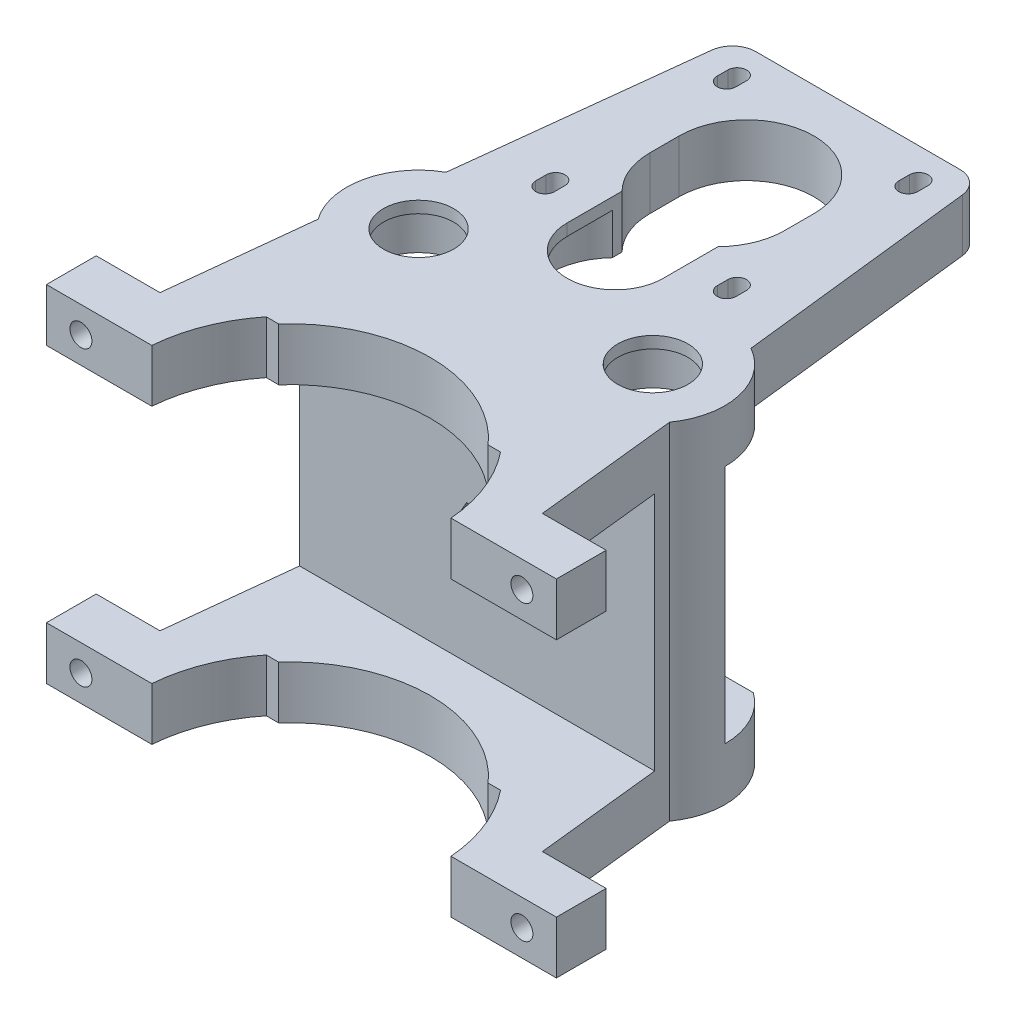
SolidWorks part; units mm, degrees
ref_plane "Alzado" through (0, 0, 0) normal (0, 0, 1) x (1, 0, 0)
ref_plane "Planta" through (0, 0, 0) normal (0, 1, 0) x (1, 0, 0)
ref_plane "Vista lateral" through (0, 0, 0) normal (1, 0, 0) x (0, 0, -1)
sketch "Croquis1" plane through (0, 0, 0) normal (0, 1, 0) x (1, 0, 0)
  line L0 (0, 78) -> (0, 73) construction
  line L1 (0, 78) -> (0, 55.57) construction
  line L2 (0, 73) -> (0, 78) construction
  line L3 (-11.5, 73) -> (-11.5, 78)
  line L4 (11.5, 73) -> (11.5, 78)
  line L5 (0, 78) -> (0, 55.57) construction
  line L6 (8.2, 78) -> (8.2, 55.57)
  line L7 (-8.2, 78) -> (-8.2, 55.57)
  line L8 (0, 0) -> (0, 10.5) construction
  line L9 (-25.5343, 2) -> (-43.5343, 2)
  line L10 (-43.5343, 2) -> (-43.5343, 10.5)
  line L11 (-43.5343, 10.5) -> (-32.6458, 10.5)
  line L12 (17.8885, 16) -> (20, 16)
  line L13 (-20, 16) -> (-17.8885, 16)
  line L14 (-32.6458, 10.5) -> (-30.0085, 34.8564)
  line L16 (26.0326, 52.719) -> (21, 97)
  line L17 (21, 97) -> (-21, 97)
  line L18 (-21, 97) -> (-26.0265, 52.7183)
  line L27 (25.5343, 2) -> (43.5343, 2)
  line L28 (43.5343, 2) -> (43.5343, 10.5)
  line L29 (43.5343, 10.5) -> (32.6458, 10.5)
  line L30 (32.6458, 10.5) -> (30.0091, 34.851)
  line L68 (-15.5, 91) -> (15.5, 91) construction
  line L69 (-15.5, 91) -> (-15.5, 60) construction
  line L70 (-15.5, 60) -> (15.5, 60) construction
  line L71 (15.5, 91) -> (15.5, 60) construction
  line L72 (-15.5, 91) -> (15.5, 60) construction
  line L73 (-15.5, 60) -> (15.5, 91) construction
  arc A0 (-11.5, 73) -> (11.5, 73) centre (0, 73) ccw
  arc A1 (11.5, 78) -> (-11.5, 78) centre (0, 78) ccw
  arc A2 (8.2, 78) -> (-8.2, 78) centre (0, 78) ccw
  arc A3 (-8.2, 55.57) -> (8.2, 55.57) centre (0, 55.57) ccw
  arc A4 (-25.5343, 2) -> (-20, 16) centre (0, 0) cw
  circle A12 centre (20, 42) radius 6
  circle A13 centre (-20, 42) radius 6
  arc A15 (17.8885, 16) -> (-17.8885, 16) centre (0, 0) ccw
  arc A18 (25.5343, 2) -> (20, 16) centre (0, 0) ccw
  arc A21 (-26.0265, 52.7183) -> (-30.0085, 34.8564) centre (-20, 42) ccw
  arc A28 (30.0091, 34.851) -> (26.0326, 52.719) centre (20, 42) ccw
  point P4 (0, 75.5)
  point P7 (0, 66.785)
  point P10 (0, 75.5)
  point P23 (0, 66.785)
  point P36 (0, 97)
  point P56 (0, 72.1)
  point P151 (0, 72.1)
  dimension "D4" = 24
  dimension "D10" = 12.2964
  dimension "D11" = 12.3
  dimension "D12" = 12
  dimension "D19" = 5
  dimension "D20" = 22.43
  dimension "D21" = 19
  dimension "D24" = 8.2
  dimension "D26" = 6
  dimension "D28" = 42
  dimension "D22" = 55
  dimension "D23" = 11.5
  dimension "D5" = 25.6125
  dimension "D3" = 40
  dimension "D6" = 8.5
  dimension "D7" = 40
  dimension "D8" = 20
  dimension "D9" = 42
  dimension "D13" = 18
  dimension "D14" = 2
  dimension "D15" = 96.18
  dimension "D16" = 2.6368
  dimension "D17" = 24.9
  dimension "D18" = 31
  dimension "D25" = 2.6373
  dimension "D27" = 12.96
extrude "Saliente-Extruir1" add sketch "Croquis1" along normal mid plane 9 contours L30 A28 L16 L17 L18 A21 L9 L11 L13 A15 L12 A18 L27 L28 L29 A12 A13 region at (0.0016, 0, -46.991)
fillet "Redondeo1" radius 4 2 edges at (-21, 0, -97) (21, 0, -97)
sketch "Croquis6" plane through (0, -4.5, 0) normal (0, -1, 0) x (1, 0, 0)
  circle A0 centre (0, -55.57) radius 11.25
  dimension "D1" = 22.5
extrude "Cortar-Extruir1" cut sketch "Croquis6" against normal blind 7
sketch "Croquis7" plane through (0, 0, -10.5) normal (0, 0, -1) x (-1, 0, 0)
  line L0 (-39.4458, 3.1177) -> (-41.2458, 0)
  line L1 (-41.2458, 0) -> (-39.4458, -3.1177)
  line L2 (-39.4458, -3.1177) -> (-35.8458, -3.1177)
  line L3 (-35.8458, -3.1177) -> (-34.0458, 0)
  line L4 (-34.0458, 0) -> (-35.8458, 3.1177)
  line L5 (-35.8458, 3.1177) -> (-39.4458, 3.1177)
  line L6 (-32.6458, 4.5) -> (-32.6458, -4.5) construction
  circle A0 centre (-37.6458, 0) radius 3.1177 construction
  circle A1 centre (-37.6458, 0) radius 1.875
  point P10 (-37.6458, 0)
  point P13 (-32.6458, 0)
  dimension "D2" = 3.75
  dimension "D4" = 6.2354
  dimension "D1" = 3.6
  dimension "D3" = 5
extrude "Cortar-Extruir2" cut sketch "Croquis7" against normal blind 2.8 contours L2 L3 L4 L5 L0 L1
extrude "Cortar-Extruir3" cut sketch "Croquis7<3>" against normal through all contours A1 region at (37.6458, 0, -10.5)
sketch "Croquis7<3>" plane through (0, 0, -10.5) normal (0, 0, -1) x (-1, 0, 0) same geometry as "Croquis7"
hole_wizard "Refrentado para tornillo con cabeza plana de M1.63" positions "Croquis10" profile "Croquis9" size "M1.6" standard "DIN" slot yes end condition through all
sketch "Croquis10" plane through (0, -4.5, 0) normal (0, -1, 0) x (-1, 0, 0)
  line L0 (-15.5, 88.5) -> (-15.5, 93.5) construction
  point P0 (-15.5, 91)
  point P5 (15.5, 91)
  point P8 (15.5, 60)
  point P11 (-15.5, 60)
  dimension "D1" = 5
sketch "Croquis9" plane through (15.5, -4.5, -91) normal (1, 0, 0) x (0, 0, -1)
  line L0 (0, 0) -> (0, 9)
  line L1 (0, 9) -> (1.6, 9)
  line L3 (1.6, 9) -> (1.6, 2.2)
  line L4 (1.6, 2.2) -> (3.6, 2.2)
  line L5 (3.6, 2.2) -> (3.6, 0)
  line L7 (3.6, 0) -> (0, 0)
  line L11 (0, -6.35) -> (0, 107.95) construction
  dimension "Diámetro de taladro hasta el siguiente" = 3.2
  dimension "Profundidad de taladro hasta el siguiente" = 9
  dimension "Diámetro de refrentado" = 7.2
  dimension "Profundidad de refrentado" = 2.2
hole_wizard "Refrentado para tornillo con cabeza plana de M1.62" positions "Croquis11" profile "Croquis13" counterbore size "M1.6" standard "DIN"
sketch "Croquis11" plane through (0, -4.5, 0) normal (0, -1, 0) x (-1, 0, 0)
  point P0 (-20, 42)
  point P3 (20, 42)
sketch "Croquis13" plane through (20, -4.5, -42) normal (1, 0, 0) x (0, 0, -1)
  line L0 (0, 0) -> (0, 10.5408)
  line L1 (0, 10.5408) -> (0.9, 10)
  line L2 (0.9, 10) -> (0.9, 7)
  line L3 (0.9, 7) -> (7.75, 7)
  line L4 (7.75, 7) -> (7.75, 0)
  line L5 (7.75, 0) -> (0, 0)
  line L10 (0, 10.5408) -> (-0.9, 10) construction
  line L11 (0, -6.35) -> (0, 107.95) construction
  dimension "Diámetro de taladro" = 1.8
  dimension "Profundidad de taladro" = 10
  dimension "Diámetro de refrentado" = 15.5
  dimension "Profundidad de refrentado" = 7
  dimension "Ángulo de perforador" = 118
mirror "Simetría1" about plane through (0, 0, 0) normal (1, 0, 0) of "Cortar-Extruir3"
mirror "Simetría2" about plane through (0, 0, 0) normal (1, 0, 0) of "Cortar-Extruir2"
sketch "Croquis15" plane through (0, -4.5, 0) normal (0, -1, 0) x (1, 0, 0)
  line L12 (32.3, -42) -> (27.75, -42)
  line L13 (-26.0265, -52.7183) -> (-21.4028, -93.4511)
  line L14 (-17.4284, -97) -> (17.4289, -97)
  line L15 (21.4033, -93.4517) -> (26.0326, -52.719)
  line L16 (30.0091, -34.851) -> (32.6458, -10.5)
  line L17 (32.6458, -10.5) -> (43.5343, -10.5)
  line L18 (43.5343, -10.5) -> (43.5343, -2)
  line L19 (43.5343, -2) -> (25.5343, -2)
  line L20 (20, -16) -> (17.8885, -16)
  line L21 (-17.8885, -16) -> (-20, -16)
  line L22 (-25.5343, -2) -> (-43.5343, -2)
  line L23 (-43.5343, -2) -> (-43.5343, -10.5)
  line L24 (-43.5343, -10.5) -> (-32.6458, -10.5)
  line L25 (-32.6458, -10.5) -> (-30.0085, -34.8564)
  line L26 (-26.0265, -52.7183) -> (-21.4028, -93.4511)
  line L27 (-17.4284, -97) -> (17.4289, -97)
  line L28 (21.4033, -93.4517) -> (26.0326, -52.719)
  line L29 (30.0091, -34.851) -> (32.6458, -10.5)
  line L30 (32.6458, -10.5) -> (43.5343, -10.5)
  line L31 (43.5343, -10.5) -> (43.5343, -2)
  line L32 (43.5343, -2) -> (25.5343, -2)
  line L33 (20, -16) -> (17.8885, -16)
  line L34 (-17.8885, -16) -> (-20, -16)
  line L35 (-25.5343, -2) -> (-43.5343, -2)
  line L36 (-43.5343, -2) -> (-43.5343, -10.5)
  line L37 (-43.5343, -10.5) -> (-32.6458, -10.5)
  line L38 (-32.6458, -10.5) -> (-30.0085, -34.8564)
  line L39 (12.25, -42) -> (-12.25, -42)
  line L40 (19.1, -60.9) -> (19.1, -59.1)
  line L41 (11.9, -59.1) -> (11.9, -60.9)
  line L42 (-8.2, -63.2721) -> (-8.2, -64.9371)
  line L43 (8.2, -64.9371) -> (8.2, -63.2721)
  line L44 (11.5, -78) -> (11.5, -73)
  line L45 (-11.5, -73) -> (-11.5, -78)
  line L46 (-8.2, -63.2721) -> (-8.2, -64.9371)
  line L47 (8.2, -64.9371) -> (8.2, -63.2721)
  line L48 (11.5, -78) -> (11.5, -73)
  line L49 (-11.5, -73) -> (-11.5, -78)
  line L50 (19.1, -60.9) -> (19.1, -59.1)
  line L51 (11.9, -59.1) -> (11.9, -60.9)
  line L52 (-11.9, -60.9) -> (-11.9, -59.1)
  line L53 (-19.1, -59.1) -> (-19.1, -60.9)
  line L54 (-11.9, -60.9) -> (-11.9, -59.1)
  line L55 (-19.1, -59.1) -> (-19.1, -60.9)
  line L56 (-11.9, -91.9) -> (-11.9, -90.1)
  line L57 (-19.1, -90.1) -> (-19.1, -91.9)
  line L58 (-11.9, -91.9) -> (-11.9, -90.1)
  line L59 (-19.1, -90.1) -> (-19.1, -91.9)
  line L60 (19.1, -91.9) -> (19.1, -90.1)
  line L61 (11.9, -90.1) -> (11.9, -91.9)
  line L62 (19.1, -91.9) -> (19.1, -90.1)
  line L63 (11.9, -90.1) -> (11.9, -91.9)
  line L64 (-27.75, -42) -> (-32.2964, -42)
  line L65 (-30.3178, -32) -> (30.3178, -32)
  arc A7 (-21.4028, -93.4511) -> (-17.4284, -97) centre (-17.4284, -93) ccw
  arc A8 (17.4289, -97) -> (21.4033, -93.4517) centre (17.4289, -93) ccw
  arc A9 (26.0326, -52.719) -> (30.0091, -34.851) centre (20, -42) ccw
  arc A10 (20, -16) -> (25.5343, -2) centre (0, 0) ccw
  arc A11 (-17.8885, -16) -> (17.8885, -16) centre (0, 0) ccw
  arc A12 (-25.5343, -2) -> (-20, -16) centre (0, 0) ccw
  arc A13 (-30.0085, -34.8564) -> (-26.0265, -52.7183) centre (-20, -42) ccw
  arc A14 (-21.4028, -93.4511) -> (-17.4284, -97) centre (-17.4284, -93) ccw
  arc A15 (17.4289, -97) -> (21.4033, -93.4517) centre (17.4289, -93) ccw
  arc A16 (26.0326, -52.719) -> (30.0091, -34.851) centre (20, -42) ccw
  arc A17 (20, -16) -> (25.5343, -2) centre (0, 0) ccw
  arc A18 (-17.8885, -16) -> (17.8885, -16) centre (0, 0) ccw
  arc A19 (-25.5343, -2) -> (-20, -16) centre (0, 0) ccw
  arc A20 (-30.0085, -34.8564) -> (-26.0265, -52.7183) centre (-20, -42) ccw
  circle A29 centre (-20, -42) radius 7.75
  arc A30 (19.1, -59.1) -> (11.9, -59.1) centre (15.5, -59.1) ccw
  arc A31 (11.9, -60.9) -> (19.1, -60.9) centre (15.5, -60.9) ccw
  arc A32 (8.2, -63.2721) -> (-8.2, -63.2721) centre (0, -55.57) ccw
  arc A33 (11.5, -73) -> (8.2, -64.9371) centre (0, -73) ccw
  arc A34 (-11.5, -78) -> (11.5, -78) centre (0, -78) ccw
  arc A35 (-8.2, -64.9371) -> (-11.5, -73) centre (0, -73) ccw
  arc A36 (8.2, -63.2721) -> (-8.2, -63.2721) centre (0, -55.57) ccw
  arc A37 (11.5, -73) -> (8.2, -64.9371) centre (0, -73) ccw
  arc A38 (-11.5, -78) -> (11.5, -78) centre (0, -78) ccw
  arc A39 (-8.2, -64.9371) -> (-11.5, -73) centre (0, -73) ccw
  arc A40 (19.1, -59.1) -> (11.9, -59.1) centre (15.5, -59.1) ccw
  arc A41 (11.9, -60.9) -> (19.1, -60.9) centre (15.5, -60.9) ccw
  arc A42 (-19.1, -60.9) -> (-11.9, -60.9) centre (-15.5, -60.9) ccw
  arc A43 (-11.9, -59.1) -> (-19.1, -59.1) centre (-15.5, -59.1) ccw
  arc A44 (-19.1, -60.9) -> (-11.9, -60.9) centre (-15.5, -60.9) ccw
  arc A45 (-11.9, -59.1) -> (-19.1, -59.1) centre (-15.5, -59.1) ccw
  arc A46 (-19.1, -91.9) -> (-11.9, -91.9) centre (-15.5, -91.9) ccw
  arc A47 (-11.9, -90.1) -> (-19.1, -90.1) centre (-15.5, -90.1) ccw
  arc A48 (-19.1, -91.9) -> (-11.9, -91.9) centre (-15.5, -91.9) ccw
  arc A49 (-11.9, -90.1) -> (-19.1, -90.1) centre (-15.5, -90.1) ccw
  arc A50 (11.9, -91.9) -> (19.1, -91.9) centre (15.5, -91.9) ccw
  arc A51 (19.1, -90.1) -> (11.9, -90.1) centre (15.5, -90.1) ccw
  arc A52 (11.9, -91.9) -> (19.1, -91.9) centre (15.5, -91.9) ccw
  arc A53 (19.1, -90.1) -> (11.9, -90.1) centre (15.5, -90.1) ccw
  circle A54 centre (-20, -42) radius 7.75
  circle A55 centre (20, -42) radius 7.75
  circle A56 centre (20, -42) radius 7.75
  circle M47 centre (20, -42) radius 7.75
  circle M48 centre (-20, -42) radius 7.75
  arc M78 (26.0326, -52.719) -> (30.0091, -34.851) centre (20, -42) ccw
  line M79 (30.0091, -34.851) -> (32.6458, -10.5)
  line M80 (32.6458, -10.5) -> (43.5343, -10.5)
  line M81 (43.5343, -10.5) -> (43.5343, -2)
  line M82 (43.5343, -2) -> (25.5343, -2)
  arc M83 (25.5343, -2) -> (20, -16) centre (0, 0) cw
  line M84 (20, -16) -> (17.8885, -16)
  arc M85 (17.8885, -16) -> (-17.8885, -16) centre (0, 0) cw
  line M86 (-17.8885, -16) -> (-20, -16)
  arc M87 (-20, -16) -> (-25.5343, -2) centre (0, 0) cw
  line M88 (-25.5343, -2) -> (-43.5343, -2)
  line M89 (-43.5343, -2) -> (-43.5343, -10.5)
  line M90 (-43.5343, -10.5) -> (-32.6458, -10.5)
  line M91 (-32.6458, -10.5) -> (-30.0085, -34.8564)
  arc M92 (-30.0085, -34.8564) -> (-26.0265, -52.7183) centre (-20, -42) ccw
  dimension "D9" = 10
  dimension "D1" = 0
  dimension "D2" = 0
  dimension "D3" = 0
  dimension "D4" = 0
  dimension "D5" = 0
  dimension "D6" = 0
  dimension "D7" = 0
  dimension "D8" = 0
extrude "Saliente-Extruir2" add sketch "Croquis15" along normal blind 50 contours L64 L39 L12 M48 M47 M78 M79 M80 M81 M82 M83 M84 M85 M86 M87 M88 M89 M90 M91 M92 | L65 L38 L64 L39 L12 M92 M48 M47 M78 M79 region at (0.002, -4.5, -36.366) region at (0, -4.5, -31.0791)
extrude "Cortar-Extruir4" cut sketch "Croquis15<3>" along normal blind 41 contours L65 L29 M91 M80 M81 M82 M83 M84 M85 M86 M87 M88 M89 M90 region at (0, -4.5, -31.0791)
sketch "Croquis15<3>" plane through (0, -4.5, 0) normal (0, -1, 0) x (1, 0, 0) same geometry as "Croquis15"
ref_plane "Plano1" through (0, -25, 0) normal (0, -1, 0) x (-1, 0, 0)
mirror "Simetría3" about plane through (0, -25, 0) normal (0, -1, 0) of "Simetría2", "Simetría1", "Cortar-Extruir3"
sketch "Croquis16" plane through (0, -54.5, 0) normal (0, -1, 0) x (1, 0, 0)
  circle A0 centre (-20, -42) radius 7.75
  circle A1 centre (-20, -42) radius 6
  circle A2 centre (20, -42) radius 6
  circle A3 centre (20, -42) radius 7.75
  circle A4 centre (-20, -42) radius 12.3
  circle A5 centre (20, -42) radius 12.3
  line M1 (-32.6458, -10.5) -> (-30.0085, -34.8564)
  arc M2 (-30.0085, -34.8564) -> (-32.2964, -42) centre (-20, -42) ccw
  line M3 (-32.2964, -42) -> (-27.75, -42)
  arc M4 (-27.75, -42) -> (-12.25, -42) centre (-20, -42) cw
  line M5 (-12.25, -42) -> (12.25, -42)
  arc M6 (12.25, -42) -> (27.75, -42) centre (20, -42) cw
  line M7 (27.75, -42) -> (32.3, -42)
  arc M8 (32.3, -42) -> (30.0091, -34.851) centre (20, -42) ccw
  dimension "D1" = 15.5
  dimension "D2" = 12
  dimension "D3" = 24.6
extrude "Saliente-Extruir3" add sketch "Croquis16" against normal blind 2 contours A0 A1 M4 | A3 A2 M6 region at (-20, -54.5, -49.5308) region at (20, -54.5, -49.5308)
extrude "Saliente-Extruir4" add sketch "Croquis16<3>" against normal up to surface (9 mm away) contours A4 M5 M1 M2 M3 M4 | A4 A0 M1 M5 M3 M2 | A5 M8 M5 M6 M7 | A5 A3 M5 M7 region at (-9.975, -54.5, -42.3136) region at (-20, -54.5, -33.975) region at (16.3304, -54.5, -30.5486) region at (9.975, -54.5, -42.275) up to face at (0, -45.5, -13.3451)
sketch "Croquis16<3>" plane through (0, -54.5, 0) normal (0, -1, 0) x (1, 0, 0) same geometry as "Croquis16"
sketch "Croquis18" plane through (0, 0, -42) normal (0, 0, -1) x (-1, 0, 0)
  line L0 (12.25, -45.5) -> (12.25, -4.5) construction
  line L1 (-12.25, -4.5) -> (12.25, -4.5) construction
  line L3 (-7.7, -21.5) -> (7.7, -21.5)
  line L4 (-7.7, -21.5) -> (-7.7, -28.5)
  line L5 (-7.7, -28.5) -> (7.7, -28.5)
  line L6 (7.7, -21.5) -> (7.7, -28.5)
  line L7 (-7.7, -21.5) -> (7.7, -28.5) construction
  line L8 (-7.7, -28.5) -> (7.7, -21.5) construction
  circle A0 centre (0, -25) radius 1.875
  point P5 (12.25, -25)
  point P9 (0, -4.5)
  dimension "D1" = 3.75
  dimension "D2" = 7
  dimension "D3" = 15.4
extrude "Cortar-Extruir6" cut sketch "Croquis18" against normal blind 5 draft 5 contours A0 | L6 L3 L4 L5 A0 region at (0, -21.6692, -42) region at (0, -25, -42)
sketch "Croquis20" plane through (0, -54.5, 0) normal (0, -1, 0) x (1, 0, 0)
  line L0 (27.1617, -52) -> (12.8383, -52)
  line L1 (7.7, -42) -> (-7.7, -42) construction
  line L2 (-12.8383, -52) -> (-27.1617, -52)
  arc A0 (-30.0091, -34.851) -> (-7.7, -42) centre (-20, -42) ccw construction
  arc A1 (7.7, -42) -> (30.0091, -34.851) centre (20, -42) ccw construction
  arc A2 (-27.1617, -52) -> (-12.8383, -52) centre (-20, -42) ccw
  arc A3 (12.8383, -52) -> (27.1617, -52) centre (20, -42) ccw
  dimension "D1" = 10
extrude "Cortar-Extruir8" cut sketch "Croquis20" against normal up to next
extrude "Cortar-Extruir9" cut sketch "Croquis18<5>" against normal through all contours A0
sketch "Croquis18<5>" plane through (0, 0, -42) normal (0, 0, -1) x (-1, 0, 0) same geometry as "Croquis18"
sketch "Croquis21" plane through (0, 0, -32) normal (0, 0, 1) x (1, 0, 0)
  line L1 (1.8, -28.1177) -> (3.6, -25)
  line L2 (3.6, -25) -> (1.8, -21.8823)
  line L3 (1.8, -21.8823) -> (-1.8, -21.8823)
  line L4 (-1.8, -21.8823) -> (-3.6, -25)
  line L5 (-3.6, -25) -> (-1.8, -28.1177)
  line L6 (-1.8, -28.1177) -> (1.8, -28.1177)
  circle A0 centre (0, -25) radius 3.1177 construction
  dimension "D1" = 3.6
extrude "Cortar-Extruir10" cut sketch "Croquis21" against normal blind 2.8
